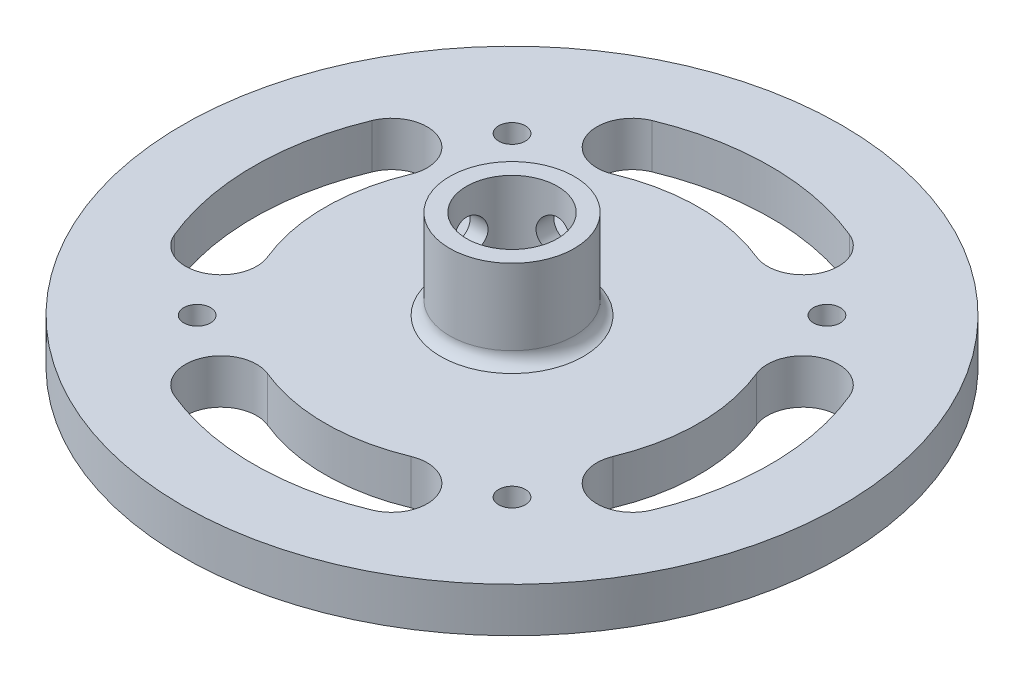
SolidWorks part; units mm, degrees
ref_plane "前视基准面" through (0, 0, 0) normal (0, 0, 1) x (1, 0, 0)
ref_plane "上视基准面" through (0, 0, 0) normal (0, 1, 0) x (1, 0, 0)
ref_plane "右视基准面" through (0, 0, 0) normal (1, 0, 0) x (0, 0, -1)
other "Configuration Table"
sketch "草图1" plane through (0, 0, 0) normal (0, 1, 0) x (1, 0, 0)
  circle A0 centre (0, 0) radius 37
  dimension "D1" = 74
extrude "凸台-拉伸1" add sketch "草图1" along normal blind 40
sketch "草图2" plane through (0, 40, 0) normal (0, 1, 0) x (1, 0, 0)
  circle A0 centre (0, 0) radius 5.1
  dimension "D1" = 10.2
extrude "切除-拉伸1" cut sketch "草图2" against normal blind 40
sketch "草图3" plane through (0, 40, 0) normal (0, 1, 0) x (1, 0, 0)
  line L0 (-1000, 0) -> (49000, 0) construction
  line L1 (0, -1000) -> (0, 49000) construction
  circle A0 centre (0, 0) radius 30
  circle A1 centre (0, 30) radius 5
  circle A3 centre (25.9808, 15) radius 5
  circle A4 centre (30, 0) radius 5
  circle A5 centre (25.9808, -15) radius 5
  circle A7 centre (0, -30) radius 5
  circle A8 centre (-15, -25.9808) radius 5
  circle A9 centre (-25.9808, -15) radius 5
  circle A11 centre (-25.9808, 15) radius 5
  circle A12 centre (-15, 25.9808) radius 5
  circle A13 centre (0, 0) radius 25
  circle A14 centre (0, 0) radius 35
  circle A15 centre (-30, 0) radius 5 [skipped]
  circle A16 centre (15, -25.9808) radius 5 [skipped]
  circle A17 centre (15, 25.9808) radius 5 [skipped]
  point P34 (0, 0)
  dimension "D1" = 60
  dimension "D2" = 10
  dimension "D3" = 12
extrude "切除-拉伸2" cut sketch "草图3" against normal blind 40 contours A0 A11 | A0 A11 | A13 A12 A0 A11 | A12 A14 A11 A0 | A0 A12 | A0 A12 | A1 A14 A12 A0 | A13 A1 A0 A12 | A0 A1 | A0 A1 | A0 A9 | A0 A9 | A9 A14 A8 A0 | A13 A9 A0 A8 | A0 A8 | A0 A8 | A8 A14 A7 A0 | A13 A8 A0 A7 | A0 A7 | A0 A7 | A0 A5 | A0 A5 | A0 A4 | A0 A4 | A0 A3 | A0 A3 | A4 A14 A3 A0 | A13 A4 A0 A3 | A13 A5 A0 A4 | A5 A14 A4 A0 region at (27.8047, 40, 0) region at (32.0453, 40, 0) region at (26.1943, 40, -7.0188) region at (31.6944, 40, -8.4925) region at (31.6944, 40, 8.4925) region at (26.1943, 40, 7.0188) region at (24.0795, 40, -13.9023) region at (27.752, 40, -16.0226) region at (27.752, 40, 16.0226) region at (24.0795, 40, 13.9023) region at (-7.0188, 40, -26.1943) region at (0, 40, -27.8047) region at (0, 40, -32.0453) region at (-8.4925, 40, -31.6944) region at (-8.4925, 40, 31.6944) region at (0, 40, 32.0453) region at (0, 40, 27.8047) region at (-7.0188, 40, 26.1943) region at (-19.1756, 40, -19.1756) region at (-13.9023, 40, -24.0795) region at (-16.0226, 40, -27.752) region at (-23.2019, 40, -23.2019) region at (-23.2019, 40, 23.2019) region at (-16.0226, 40, 27.752) region at (-13.9023, 40, 24.0795) region at (-19.1756, 40, 19.1756) region at (-24.0795, 40, -13.9023) region at (-27.752, 40, -16.0226) region at (-27.752, 40, 16.0226) region at (-24.0795, 40, 13.9023)
sketch "草图4" plane through (0, 40, 0) normal (0, 1, 0) x (1, 0, 0)
  circle A0 centre (0, 0) radius 7
  circle A1 centre (0, 0) radius 5.1
  dimension "D1" = 14
extrude "凸台-拉伸2" add sketch "草图4" along normal mid plane 20
sketch "草图5" plane through (0, 0, 0) normal (0, -1, 0) x (1, 0, 0)
  circle A0 centre (0, 0) radius 5.1
sketch "草图6" plane through (0, 0, 0) normal (0, 0, 1) x (1, 0, 0)
  line L0 (0, 50) -> (0, 45)
  line L1 (5.1, 50) -> (-5.1, 50) construction
  circle A0 centre (0, 45) radius 2
  dimension "D2" = 4
  dimension "D1" = 5
extrude "切除-拉伸3" cut sketch "草图6" against normal up to next contours A0 region at (-1.3742, 43.6258, 0)
sketch "草图7" plane through (0, 0, 0) normal (1, 0, 0) x (0, 0, -1)
  line L0 (0, 50) -> (0, 45)
  line L1 (7, 50) -> (-7, 50) construction
  circle A0 centre (0, 45) radius 2
  dimension "D2" = 4
  dimension "D1" = 5
extrude "切除-拉伸4" cut sketch "草图7" against normal up to next contours A0 region at (0, 43.6258, 1.3742)
sketch "草图10" plane through (0, 0, 0) normal (0, -1, 0) x (1, 0, 0)
  line L0 (0, 0) -> (0, 37)
  line L1 (0, 0) -> (7.2183, 36.2891)
  line L2 (0, 0) -> (14.1593, 34.1835)
  line L3 (0, 0) -> (20.5561, 30.7644)
  line L4 (0, 0) -> (26.163, 26.163)
  line L5 (0, 0) -> (30.7644, 20.5561)
  line L6 (0, 0) -> (34.1835, 14.1593)
  line L7 (0, 0) -> (36.2891, 7.2183)
  line L8 (0, 0) -> (37, 0)
  line L9 (0, 0) -> (36.2891, -7.2183)
  line L10 (0, 0) -> (34.1835, -14.1593)
  line L11 (0, 0) -> (30.7644, -20.5561)
  line L12 (0, 0) -> (26.163, -26.163)
  line L13 (0, 0) -> (20.5561, -30.7644)
  line L14 (0, 0) -> (14.1593, -34.1835)
  line L15 (0, 0) -> (7.2183, -36.2891)
  line L16 (0, 0) -> (0, -37)
  line L17 (0, 0) -> (-7.2183, -36.2891)
  line L18 (0, 0) -> (-14.1593, -34.1835)
  line L19 (0, 0) -> (-20.5561, -30.7644)
  line L20 (0, 0) -> (-26.163, -26.163)
  line L21 (0, 0) -> (-30.7644, -20.5561)
  line L22 (0, 0) -> (-34.1835, -14.1593)
  line L23 (0, 0) -> (-36.2891, -7.2183)
  line L24 (0, 0) -> (-37, 0)
  line L25 (0, 0) -> (-36.2891, 7.2183)
  line L26 (0, 0) -> (-34.1835, 14.1593)
  line L27 (0, 0) -> (-30.7644, 20.5561)
  line L28 (0, 0) -> (-26.163, 26.163)
  line L29 (0, 0) -> (-20.5561, 30.7644)
  line L30 (0, 0) -> (-14.1593, 34.1835)
  line L31 (0, 0) -> (-7.2183, 36.2891)
  circle A0 centre (0, 0) radius 37
  circle A1 centre (0, 0) radius 36
  point P38 (0, 0)
  circle M14 centre (0, 0) radius 37
  dimension "D1" = 72
  dimension "D2" = 37
  dimension "D3" = 32
extrude "切除-拉伸7" cut sketch "草图10" against normal up to next contours A1 L26 L25 M14 | A1 L27 L26 M14 | A1 L28 L27 M14 | A1 L30 L29 M14 | A1 L31 L30 M14 | A1 L0 L31 M14 | A1 L2 L1 M14 | A1 L3 L2 M14 | A1 L4 L3 M14 | A1 L6 L5 M14 | A1 L7 L6 M14 | A1 L8 L7 M14 | A1 L10 L9 M14 | A1 L11 L10 M14 | A1 L12 L11 M14 | A1 L14 L13 M14 | A1 L15 L14 M14 | A1 L16 L15 M14 | A1 L18 L17 M14 | A1 L19 L18 M14 | A1 L20 L19 M14 | A1 L22 L21 M14 | A1 L23 L22 M14 | A1 L24 L23 M14 region at (-3.5721, 0, 36.2682) region at (10.579, 0, 34.8744) region at (17.1794, 0, 32.1405) region at (23.1196, 0, 28.1713) region at (32.1405, 0, 17.1794) region at (34.8744, 0, 10.579) region at (36.2682, 0, 3.5721) region at (34.8744, 0, -10.579) region at (32.1405, 0, -17.1794) region at (28.1713, 0, -23.1196) region at (17.1794, 0, -32.1405) region at (10.579, 0, -34.8744) region at (3.5721, 0, -36.2682) region at (-10.579, 0, -34.8744) region at (-17.1794, 0, -32.1405) region at (-23.1196, 0, -28.1713) region at (-32.1405, 0, -17.1794) region at (-34.8744, 0, -10.579) region at (-36.2682, 0, -3.5721) region at (-34.8744, 0, 10.579) region at (-32.1405, 0, 17.1794) region at (-28.1713, 0, 23.1196) region at (-17.1794, 0, 32.1405) region at (-10.579, 0, 34.8744)
sketch "草图14" plane through (0, 40, 0) normal (0, 1, 0) x (1, 0, 0)
  circle A0 centre (0, 0) radius 36
extrude "凸台-拉伸4" add sketch "草图14" against normal blind 40
sketch "草图15" plane through (0, 40, 0) normal (0, 1, 0) x (1, 0, 0)
  circle A0 centre (0, 0) radius 25
  circle A1 centre (0, 25) radius 5
  circle A2 centre (12.5, 21.6506) radius 5
  circle A3 centre (21.6506, 12.5) radius 5
  circle A4 centre (25, 0) radius 5
  circle A5 centre (21.6506, -12.5) radius 5
  circle A6 centre (12.5, -21.6506) radius 5
  circle A7 centre (0, -25) radius 5
  circle A8 centre (-12.5, -21.6506) radius 5
  circle A9 centre (-21.6506, -12.5) radius 5
  circle A10 centre (-25, 0) radius 5
  circle A11 centre (-21.6506, 12.5) radius 5
  circle A12 centre (-12.5, 21.6506) radius 5
  circle A13 centre (0, 0) radius 30
  circle A14 centre (0, 0) radius 20
  point P30 (0, 0)
  dimension "D1" = 50
  dimension "D2" = 10
  dimension "D3" = 12
extrude "切除-拉伸11" cut sketch "草图15" against normal blind 40 contours A14 A12 A0 A11 | A12 A13 A11 A0 | A0 A11 | A0 A11 | A0 A12 | A0 A12 | A0 A1 | A0 A1 | A2 A13 A1 A0 | A14 A2 A0 A1 | A0 A2 | A0 A2 | A0 A3 | A0 A3 | A14 A4 A0 A3 | A4 A13 A3 A0 | A0 A4 | A0 A4 | A0 A5 | A0 A5 | A0 A6 | A0 A6 | A14 A6 A0 A5 | A6 A13 A5 A0 | A0 A7 | A0 A7 | A0 A8 | A0 A8 | A8 A13 A7 A0 | A14 A8 A0 A7 | A0 A9 | A0 A9 | A14 A10 A0 A9 | A10 A13 A9 A0 | A0 A10 | A0 A10 region at (22.7904, 40, 0) region at (27.0295, 40, 0) region at (21.2179, 40, -5.6853) region at (27.0803, 40, -7.2562) region at (19.7371, 40, -11.3952) region at (23.4082, 40, -13.5147) region at (23.4082, 40, 13.5147) region at (19.7371, 40, 11.3952) region at (19.8242, 40, 19.8242) region at (15.5326, 40, 15.5326) region at (11.3952, 40, -19.7371) region at (13.5147, 40, -23.4082) region at (5.6853, 40, -21.2179) region at (7.2562, 40, -27.0803) region at (13.5147, 40, 23.4082) region at (11.3952, 40, 19.7371) region at (0, 40, -22.7904) region at (0, 40, -27.0295) region at (-7.2562, 40, 27.0803) region at (0, 40, 27.0295) region at (0, 40, 22.7904) region at (-5.6853, 40, 21.2179) region at (-15.5326, 40, -15.5326) region at (-11.3952, 40, -19.7371) region at (-13.5147, 40, -23.4082) region at (-19.8242, 40, -19.8242) region at (-13.5147, 40, 23.4082) region at (-11.3952, 40, 19.7371) region at (-19.7371, 40, -11.3952) region at (-23.4082, 40, -13.5147) region at (-27.0803, 40, 7.2562) region at (-23.4082, 40, 13.5147) region at (-19.7371, 40, 11.3952) region at (-21.2179, 40, 5.6853) region at (-22.7904, 40, 0) region at (-27.0295, 40, 0)
sketch "草图17" plane through (0, 40, 0) normal (0, 1, 0) x (1, 0, 0)
  circle A0 centre (0, 0) radius 5.1
extrude "切除-拉伸12" cut sketch "草图17" against normal blind 40
ref_plane "基准面2" through (0, 20, 0) normal (0, 1, 0) x (1, 0, 0)
sketch "草图18" plane through (0, 20, 0) normal (0, 1, 0) x (1, 0, 0)
  line L0 (-27.5, 0) -> (27.5, 0) construction
  circle A0 centre (0, 0) radius 37
  circle A1 centre (0, 0) radius 10
  dimension "D1" = 20
sketch "草图20" plane through (0, 0, 0) normal (0, 0, 1) x (1, 0, 0)
  line L0 (-7, 40) -> (-7, 41.5)
  line L2 (-7, 43.0001) -> (-7, 40) construction
  line L3 (0, 40) -> (-20.0005, 40) construction
  line L4 (-8.0182, 40) -> (-7, 40)
  line L5 (0, -950) -> (0, 49050) construction
  line L6 (7, 50) -> (-7, 50) construction
  arc A0 (-7, 41.5) -> (-8.0182, 40) centre (-8.6141, 41.5) cw
  point P14 (0, 50)
revolve "旋转1" add sketch "草图20" angle 360 about L5
sketch "草图21" plane through (0, 0, 0) normal (0, -1, 0) x (1, 0, 0)
  circle A0 centre (0, 0) radius 37
extrude "切除-拉伸14" cut sketch "草图21" against normal blind 35
sketch "草图23" plane through (0, 35, 0) normal (0, -1, 0) x (1, 0, 0)
  circle A0 centre (0, 0) radius 5.1
  circle A1 centre (0, 0) radius 30
extrude "凸台-拉伸5" add sketch "草图23" against normal blind 5
sketch "草图24" plane through (0, 35, 0) normal (0, -1, 0) x (1, 0, 0)
  circle A0 centre (0, 0) radius 25
  circle A1 centre (0, 25) radius 4
  circle A2 centre (9.5671, 23.097) radius 4
  circle A3 centre (17.6777, 17.6777) radius 4
  circle A4 centre (23.097, 9.5671) radius 4
  circle A5 centre (25, 0) radius 4
  circle A6 centre (23.097, -9.5671) radius 4
  circle A7 centre (17.6777, -17.6777) radius 4
  circle A8 centre (9.5671, -23.097) radius 4
  circle A9 centre (0, -25) radius 4
  circle A10 centre (-9.5671, -23.097) radius 4
  circle A11 centre (-17.6777, -17.6777) radius 4
  circle A12 centre (-23.097, -9.5671) radius 4
  circle A13 centre (-25, 0) radius 4
  circle A14 centre (-23.097, 9.5671) radius 4
  circle A15 centre (-17.6777, 17.6777) radius 4
  circle A16 centre (-9.5671, 23.097) radius 4
  circle A17 centre (0, 0) radius 29
  circle A18 centre (0, 0) radius 21
  point P37 (0, 0)
  dimension "D1" = 50
  dimension "D2" = 8
  dimension "D3" = 16
extrude "切除-拉伸15" cut sketch "草图24" against normal blind 5 contours A0 A16 | A0 A16 | A18 A1 A0 A16 | A1 A17 A16 A0 | A0 A1 | A0 A1 | A18 A2 A0 A1 | A2 A17 A1 A0 | A0 A2 | A0 A2 | A0 A4 | A0 A4 | A18 A5 A0 A4 | A5 A17 A4 A0 | A0 A5 | A0 A5 | A18 A6 A0 A5 | A6 A17 A5 A0 | A0 A6 | A0 A6 | A0 A8 | A0 A8 | A0 A9 | A0 A9 | A18 A9 A0 A8 | A9 A17 A8 A0 | A18 A10 A0 A9 | A10 A17 A9 A0 | A0 A10 | A0 A10 | A0 A12 | A0 A12 | A13 A17 A12 A0 | A18 A13 A0 A12 | A0 A13 | A0 A13 | A18 A14 A0 A13 | A14 A17 A13 A0 | A0 A14 | A0 A14 region at (23.246, 35, 0) region at (26.6387, 35, 0) region at (22.0448, 35, 4.385) region at (26.995, 35, 5.3696) region at (26.995, 35, -5.3696) region at (22.0448, 35, -4.385) region at (21.4765, 35, 8.8959) region at (24.611, 35, 10.1942) region at (24.611, 35, -10.1942) region at (21.4765, 35, -8.8959) region at (4.385, 35, 22.0448) region at (8.8959, 35, 21.4765) region at (10.1942, 35, 24.611) region at (5.3696, 35, 26.995) region at (5.3696, 35, -26.995) region at (10.1942, 35, -24.611) region at (8.8959, 35, -21.4765) region at (4.385, 35, -22.0448) region at (-4.385, 35, 22.0448) region at (0, 35, 23.246) region at (0, 35, 26.6387) region at (-5.3696, 35, 26.995) region at (-5.3696, 35, -26.995) region at (0, 35, -26.6387) region at (0, 35, -23.246) region at (-4.385, 35, -22.0448) region at (-8.8959, 35, 21.4765) region at (-10.1942, 35, 24.611) region at (-10.1942, 35, -24.611) region at (-8.8959, 35, -21.4765) region at (-22.0448, 35, 4.385) region at (-21.4765, 35, 8.8959) region at (-24.611, 35, 10.1942) region at (-26.995, 35, 5.3696) region at (-26.995, 35, -5.3696) region at (-24.611, 35, -10.1942) region at (-21.4765, 35, -8.8959) region at (-22.0448, 35, -4.385) region at (-23.246, 35, 0) region at (-26.6387, 35, 0)
sketch "草图25" plane through (0, 35, 0) normal (0, -1, 0) x (1, 0, 0)
  circle A0 centre (0, 0) radius 25
  circle A1 centre (0, 25) radius 1.5
  circle A2 centre (9.5671, 23.097) radius 1.5
  circle A3 centre (17.6777, 17.6777) radius 1.5
  circle A4 centre (23.097, 9.5671) radius 1.5
  circle A5 centre (25, 0) radius 1.5
  circle A6 centre (23.097, -9.5671) radius 1.5
  circle A7 centre (17.6777, -17.6777) radius 1.5
  circle A8 centre (9.5671, -23.097) radius 1.5
  circle A9 centre (0, -25) radius 1.5
  circle A10 centre (-9.5671, -23.097) radius 1.5
  circle A11 centre (-17.6777, -17.6777) radius 1.5
  circle A12 centre (-23.097, -9.5671) radius 1.5
  circle A13 centre (-25, 0) radius 1.5
  circle A14 centre (-23.097, 9.5671) radius 1.5
  circle A15 centre (-17.6777, 17.6777) radius 1.5
  circle A16 centre (-9.5671, 23.097) radius 1.5
  point P39 (0, 0)
  dimension "D1" = 3
  dimension "D2" = 16
extrude "切除-拉伸16" cut sketch "草图25" against normal blind 5 contours A0 A15 | A0 A15 | A3 | A7 | A11 region at (-17.2218, 35, 17.2218) region at (-18.122, 35, 18.122)
sketch "草图26" plane through (0, 35, 0) normal (0, -1, 0) x (1, 0, 0)
  line L0 (-17.6777, 17.6777) -> (-17.6777, 20.1777)
  line L1 (-1000, 0) -> (49000, 0) construction
  line L2 (0, -1000) -> (0, 49000) construction
  circle A0 centre (-17.6777, 17.6777) radius 2.5
  circle A1 centre (-17.6777, 20.1777) radius 0.5
  circle A2 centre (-15.1777, 17.6777) radius 0.5
  circle A3 centre (-17.6777, 15.1777) radius 0.5
  circle A4 centre (-20.1777, 17.6777) radius 0.5
  circle A5 centre (-15.1777, -17.6777) radius 0.5
  circle A6 centre (-20.1777, -17.6777) radius 0.5
  circle A7 centre (-17.6777, -15.1777) radius 0.5
  circle A8 centre (-17.6777, -20.1777) radius 0.5
  circle A9 centre (20.1777, -17.6777) radius 0.5
  circle A10 centre (17.6777, -20.1777) radius 0.5
  circle A11 centre (15.1777, -17.6777) radius 0.5
  circle A12 centre (17.6777, -15.1777) radius 0.5
  circle A13 centre (15.1777, 17.6777) radius 0.5
  circle A14 centre (17.6777, 15.1777) radius 0.5
  circle A15 centre (17.6777, 20.1777) radius 0.5
  circle A16 centre (20.1777, 17.6777) radius 0.5
  dimension "D1" = 5
  dimension "D2" = 4
extrude "切除-拉伸18" cut sketch "草图26" against normal blind 2 contours A4 | A1 | A3 | A2 | A7 | A6 | A8 | A5 | A9 | A11 | A10 | A12 | A15 | A13 | A14 | A16
sketch "草图27" plane through (0, 40, 0) normal (0, 1, 0) x (1, 0, 0)
  circle A0 centre (0, 0) radius 36
  circle A1 centre (0, 0) radius 37
extrude "凸台-拉伸6" add sketch "草图27" against normal blind 5
